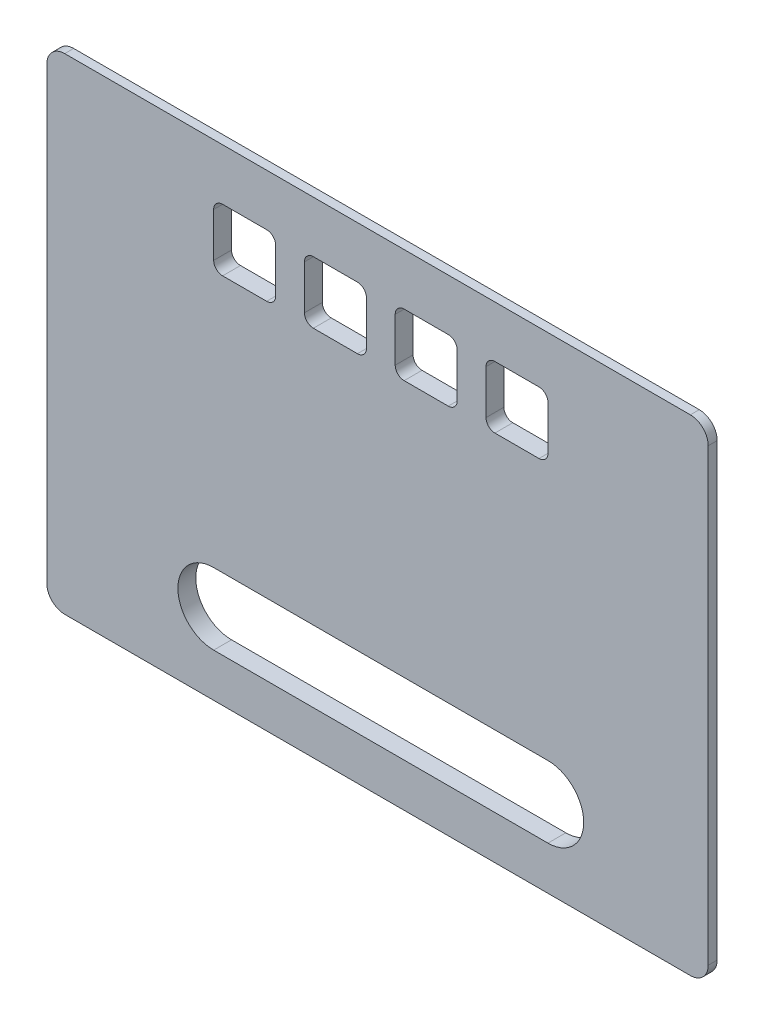
SolidWorks part; units mm, degrees
ref_plane "Спереди" through (0, 0, 0) normal (0, 0, 1) x (1, 0, 0)
ref_plane "Сверху" through (0, 0, 0) normal (0, 1, 0) x (1, 0, 0)
ref_plane "Справа" through (0, 0, 0) normal (1, 0, 0) x (0, 0, -1)
other "Configuration Table"
sketch "Эскиз1" plane through (0, 0, 0) normal (0, 0, 1) x (1, 0, 0)
  line L1 (1, 3) -> (106, 3)
  line L2 (1, 3) -> (1, 77)
  line L3 (1, 77) -> (106, 77)
  line L4 (106, 3) -> (106, 77)
extrude "Бобышка-Вытянуть1" add sketch "Эскиз1" along normal blind 3
sketch "Эскиз2" plane through (0, 0, 0) normal (0, 0, 1) x (1, 0, 0)
  line L1 (-2, 0) -> (109, 0)
  line L2 (-2, 0) -> (-2, 80)
  line L3 (-2, 80) -> (109, 80)
  line L4 (109, 0) -> (109, 80)
extrude "Бобышка-Вытянуть2" add sketch "Эскиз2" along normal blind 1.5 from offset 1.5
sketch "Эскиз3" plane through (0.75, 0, 3) normal (0, 0, 1) x (1, 0, 0)
  line L0 (25.25, 13.3) -> (81.35, 13.3) construction
  line L1 (25.25, 62.45) -> (35.65, 62.45)
  line L2 (25.25, 62.45) -> (25.25, 72.85)
  line L3 (25.25, 72.85) -> (35.65, 72.85)
  line L4 (35.65, 62.45) -> (35.65, 72.85)
  line L5 (40.483, 62.45) -> (50.883, 62.45)
  line L6 (40.483, 62.45) -> (40.483, 72.85)
  line L7 (40.483, 72.85) -> (50.883, 72.85)
  line L8 (50.883, 62.45) -> (50.883, 72.85)
  line L9 (55.717, 62.45) -> (66.117, 62.45)
  line L10 (55.717, 62.45) -> (55.717, 72.85)
  line L11 (55.717, 72.85) -> (66.117, 72.85)
  line L12 (66.117, 62.45) -> (66.117, 72.85)
  line L13 (70.95, 62.45) -> (81.35, 62.45)
  line L14 (70.95, 62.45) -> (70.95, 72.85)
  line L15 (70.95, 72.85) -> (81.35, 72.85)
  line L16 (81.35, 62.45) -> (81.35, 72.85)
  line L19 (25.25, 19.3) -> (81.35, 19.3)
  line L20 (25.25, 7.3) -> (81.35, 7.3)
  arc A2 (25.25, 19.3) -> (25.25, 7.3) centre (25.25, 13.3) ccw
  arc A3 (81.35, 7.3) -> (81.35, 19.3) centre (81.35, 13.3) ccw
  point P18 (53.3, 13.3)
extrude "Вырез-Вытянуть1" cut sketch "Эскиз3" against normal blind 5
sketch "Эскиз4" plane through (0, 0, 0) normal (0, 0, 1) x (1, 0, 0)
  line L1 (1, 77) -> (106, 77)
  line L2 (1, 77) -> (1, 78.5)
  line L3 (1, 78.5) -> (106, 78.5)
  line L4 (106, 77) -> (106, 78.5)
extrude "top_rear_inner_extension_1p5mm" add sketch "Эскиз4" along normal blind 3
sketch "Эскиз5" plane through (0, 0, 0) normal (0, 0, 1) x (1, 0, 0)
  line L1 (-2, 80) -> (109, 80)
  line L2 (-2, 80) -> (-2, 81.5)
  line L3 (-2, 81.5) -> (109, 81.5)
  line L4 (109, 80) -> (109, 81.5)
extrude "top_rear_outer_skin_extension_1p5mm" add sketch "Эскиз5" along normal blind 1.5 from offset 1.5
fillet "tool_D3_R1p5_button_corners" radius 1.5 16 edges at (71.7, 72.85, 1.5) (82.1, 72.85, 1.5) (82.1, 62.45, 1.5) (71.7, 62.45, 1.5) (56.467, 72.85, 1.5) (66.867, 72.85, 1.5) (66.867, 62.45, 1.5) (56.467, 62.45, 1.5) (41.233, 72.85, 1.5) (51.633, 72.85, 1.5) (51.633, 62.45, 1.5) (41.233, 62.45, 1.5) (26, 62.45, 1.5) (36.4, 62.45, 1.5) (36.4, 72.85, 1.5) (26, 72.85, 1.5) tangent propagation no
fillet "tool_D3_R3_top_outer_contour" radius 3 4 edges at (-2, 81.5, 2.25) (109, 81.5, 2.25) (109, 0, 2.25) (-2, 0, 2.25)
sketch "Эскиз6" plane through (0, 0, 0) normal (0, 0, -1) x (-1, 0, 0)
  circle A0 centre (-1, 10) radius 1.5
  circle A1 centre (-106, 10) radius 1.5
  circle A2 centre (-1, 40.75) radius 1.5
  circle A3 centre (-106, 40.75) radius 1.5
  circle A4 centre (-1, 71.5) radius 1.5
  circle A5 centre (-106, 71.5) radius 1.5
extrude "top_planar_edge_semicircle_pockets_D3_depth1p5_6x" cut sketch "Эскиз6" against normal blind 1.5
